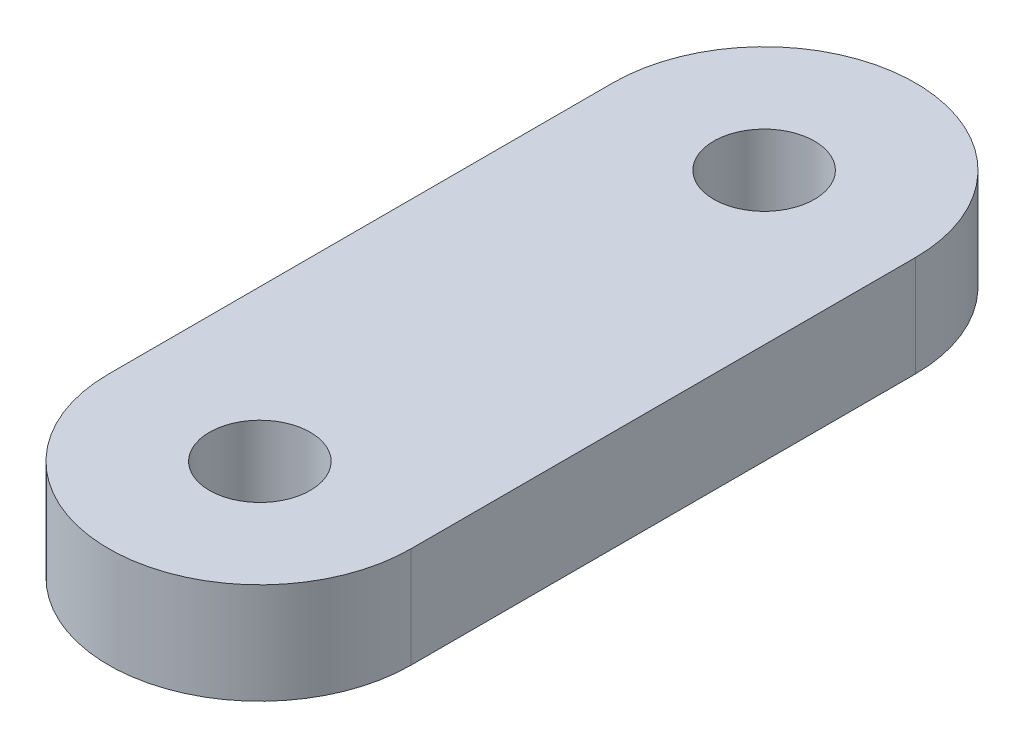
SolidWorks part; units mm, degrees
ref_plane "Front Plane" through (0, 0, 0) normal (0, 0, 1) x (1, 0, 0)
ref_plane "Top Plane" through (0, 0, 0) normal (0, 1, 0) x (1, 0, 0)
ref_plane "Right Plane" through (0, 0, 0) normal (1, 0, 0) x (0, 0, -1)
sketch "Sketch1" plane through (0, 0, 0) normal (0, 1, 0) x (1, 0, 0)
  line L2 (-1.5, 2.5) -> (-1.5, -2.5)
  line L4 (1.5, 2.5) -> (1.5, -2.5)
  line L5 (-1.5, 2.5) -> (1.5, -2.5) construction
  line L6 (-1.5, -2.5) -> (1.5, 2.5) construction
  arc A0 (1.5, 2.5) -> (-1.5, 2.5) centre (0, 2.5) ccw
  arc A1 (-1.5, -2.5) -> (1.5, -2.5) centre (0, -2.5) ccw
  circle A2 centre (0, -2.5) radius 0.5
  circle A3 centre (0, 2.5) radius 0.5
  point P0 (0, 0)
  dimension "D3" = 1
  dimension "D4" = 1
  dimension "D1" = 3
  dimension "D2" = 5
extrude "Boss-Extrude1" add sketch "Sketch1" along normal blind 1
